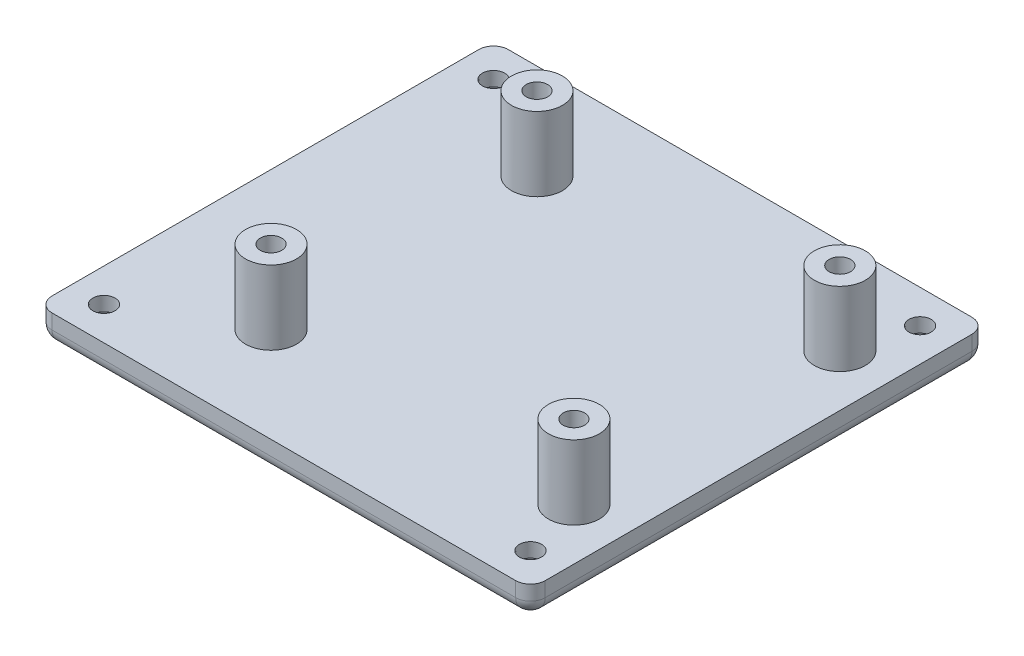
SolidWorks part; units mm, degrees
ref_plane "Front Plane" through (0, 0, 0) normal (0, 0, 1) x (1, 0, 0)
ref_plane "Top Plane" through (0, 0, 0) normal (0, 1, 0) x (1, 0, 0)
ref_plane "Right Plane" through (0, 0, 0) normal (1, 0, 0) x (0, 0, -1)
sketch "Sketch1" plane through (0, 0, 0) normal (0, 1, 0) x (1, 0, 0)
  line L1 (0, 0) -> (66.76, 0)
  line L2 (0, 0) -> (0, 61.76)
  line L3 (0, 61.76) -> (66.76, 61.76)
  line L4 (66.76, 0) -> (66.76, 61.76)
  dimension "D1" = 66.76
  dimension "D2" = 61.76
extrude "Boss-Extrude3" add sketch "Sketch1" against normal blind 4
sketch "Sketch2" plane through (0, 0, 0) normal (0, 1, 0) x (1, 0, 0)
  line L0 (63.76, 8.88) -> (14.76, 8.88) construction
  line L1 (0, 61.76) -> (0, 0) construction
  line L2 (18.76, 12.88) -> (59.76, 12.88) construction
  line L3 (0, 0) -> (66.76, 0) construction
  line L4 (66.76, 0) -> (66.76, 61.76) construction
  line L5 (66.76, 61.76) -> (0, 61.76) construction
  line L6 (63.76, 59.75) -> (63.76, 2.01) construction
  line L7 (2.01, 2.01) -> (64.75, 2.01) construction
  line L8 (2.01, 2.01) -> (2.01, 59.75) construction
  line L9 (2.01, 59.75) -> (64.75, 59.75) construction
  line L10 (64.75, 2.01) -> (64.75, 59.75) construction
  line L11 (18.76, 12.88) -> (18.76, 48.88) construction
  line L12 (18.76, 48.88) -> (59.76, 48.88) construction
  line L13 (59.76, 12.88) -> (59.76, 48.88) construction
  line L14 (14.76, 8.88) -> (14.76, 52.88) construction
  line L15 (14.76, 52.88) -> (63.76, 52.88) construction
  line L16 (0, 30.88) -> (66.76, 30.88) construction
  line L17 (39.26, 12.88) -> (39.26, 48.88) construction
  circle A0 centre (59.76, 12.88) radius 1.45
  circle A4 centre (59.76, 12.88) radius 3.45
  circle A5 centre (18.76, 12.88) radius 3.45
  circle A6 centre (18.76, 12.88) radius 1.45
  circle A7 centre (18.76, 48.88) radius 1.45
  circle A8 centre (59.76, 48.88) radius 1.45
  circle A9 centre (59.76, 48.88) radius 3.45
  circle A10 centre (18.76, 48.88) radius 3.45
  dimension "D13" = 2.9
  dimension "D11" = 6.9
  dimension "D1" = 2.01
  dimension "D2" = 2.01
  dimension "D3" = 0.99
  dimension "D4" = 2.01
  dimension "D5" = 2.01
  dimension "D6" = 49
  dimension "D7" = 44
  dimension "D8" = 22
  dimension "D9" = 4
  dimension "D10" = 4
  dimension "D12" = 4
extrude "Boss-Extrude4" add sketch "Sketch2" along normal blind 10
sketch "Sketch3" plane through (0, 0, 0) normal (0, 1, 0) x (1, 0, 0)
  line L0 (0, 61.76) -> (0, 0) construction
  line L1 (33.38, 59.75) -> (33.38, 2.01) construction
  line L2 (2.01, 30.88) -> (64.75, 30.88) construction
  line L3 (2.01, 59.75) -> (64.75, 59.75) construction
  line L6 (2.01, 59.75) -> (2.01, 2.01) construction
  line L11 (2.01, 2.01) -> (64.75, 2.01) construction
  line L12 (64.75, 59.75) -> (64.75, 2.01) construction
  line L13 (0, 0) -> (66.76, 0) construction
  line L14 (66.76, 61.76) -> (0, 61.76) construction
  line L15 (66.76, 0) -> (66.76, 61.76) construction
  circle A0 centre (4.51, 57.25) radius 1.5
  circle A1 centre (62.25, 57.25) radius 1.5
  circle A2 centre (62.25, 4.51) radius 1.5
  circle A3 centre (4.51, 4.51) radius 1.5
  dimension "D5" = 3
  dimension "D1" = 2.01
  dimension "D2" = 2.01
  dimension "D3" = 2.01
  dimension "D4" = 2.01
  dimension "D6" = 2.5
  dimension "D7" = 2.5
extrude "Cut-Extrude1" cut sketch "Sketch3" against normal blind 3 draft 3 draft outward yes
sketch "Sketch5" plane through (0, -4, 0) normal (0, -1, 0) x (1, 0, 0)
  line L0 (33.38, -4.51) -> (33.38, -57.6662) construction
  line L1 (4.51, -4.51) -> (62.25, -4.51) construction
  line L2 (4.51, -4.51) -> (4.51, -57.25) construction
  line L3 (4.51, -57.25) -> (62.25, -57.25) construction
  line L4 (62.25, -4.51) -> (62.25, -57.25) construction
  line L5 (4.51, -30.88) -> (62.25, -30.88) construction
  circle A0 centre (4.51, -4.51) radius 3
  circle A1 centre (62.25, -4.51) radius 3
  circle A2 centre (62.25, -57.25) radius 3
  circle A3 centre (4.51, -57.25) radius 3
  point P10 (33.38, -30.88)
  dimension "D1" = 6
fillet "Fillet2" radius 2 4 edges at (0, -2, 0) (66.76, -2, 0) (66.76, -2, -61.76) (0, -2, -61.76)
fillet "Fillet1" radius 2 8 edges at (66.76, -4, -30.88) (33.38, -4, -61.76) (0, -4, -30.88) (33.38, -4, 0) (0.5858, -4, -0.5858) (0.5858, -4, -61.1742) (66.1742, -4, -61.1742) (66.1742, -4, -0.5858)
extrude "Cut-Extrude2" cut sketch "Sketch5" against normal blind 2 draft 1
sketch "Sketch6" plane through (0, -4, 0) normal (0, -1, 0) x (1, 0, 0)
  line L0 (33.38, -59.76) -> (33.38, -2) construction
  line L1 (6.1531, -59.76) -> (60.6069, -59.76) construction
  line L2 (60.6069, -2) -> (6.1531, -2) construction
  line L3 (64.76, -54.76) -> (2, -54.76) construction
  line L4 (64.76, -55.6069) -> (64.76, -6.1531) construction
  line L5 (2, -6.1531) -> (2, -55.6069) construction
  line L6 (62.25, -4.51) -> (62.25, -54.76) construction
  line L7 (35.88, -54.76) -> (35.88, -2) construction
  line L8 (30.88, -54.76) -> (30.88, -2) construction
  line L9 (4.51, -4.51) -> (4.51, -54.76) construction
  line L10 (62.25, -50.76) -> (35.88, -50.76) construction
  line L11 (49.065, -50.76) -> (49.065, -2) construction
  line L12 (30.87, -50.76) -> (4.5, -50.76) construction
  line L13 (30.87, -46.76) -> (4.5, -46.76) construction
  line L14 (30.87, -42.76) -> (4.5, -42.76) construction
  line L15 (30.87, -38.76) -> (4.5, -38.76) construction
  line L16 (30.87, -34.76) -> (4.5, -34.76) construction
  line L17 (30.87, -30.76) -> (4.5, -30.76) construction
  line L18 (30.87, -26.76) -> (4.5, -26.76) construction
  line L19 (30.87, -22.76) -> (4.5, -22.76) construction
  line L20 (30.87, -18.76) -> (4.5, -18.76) construction
  line L21 (30.87, -14.76) -> (4.5, -14.76) construction
  line L22 (30.87, -10.76) -> (4.5, -10.76) construction
  line L23 (30.87, -6.76) -> (4.5, -6.76) construction
  line L24 (62.25, -46.76) -> (35.88, -46.76) construction
  line L25 (62.25, -42.76) -> (35.88, -42.76) construction
  line L26 (62.25, -38.76) -> (35.88, -38.76) construction
  line L27 (62.25, -34.76) -> (35.88, -34.76) construction
  line L28 (62.25, -30.76) -> (35.88, -30.76) construction
  line L29 (62.25, -26.76) -> (35.88, -26.76) construction
  line L30 (62.25, -22.76) -> (35.88, -22.76) construction
  line L31 (62.25, -18.76) -> (35.88, -18.76) construction
  line L32 (62.25, -14.76) -> (35.88, -14.76) construction
  line L33 (62.25, -10.76) -> (35.88, -10.76) construction
  line L34 (62.25, -6.76) -> (35.88, -6.76) construction
  line L35 (62.25, -2) -> (35.88, -2) construction
  line L36 (30.88, -2) -> (4.51, -2) construction
  line L37 (62.25, -4.51) -> (62.25, -1.9267) construction
  line L38 (35.88, -2.76) -> (62.25, -2.76) construction
  line L39 (30.88, -2.76) -> (4.51, -2.76) construction
  text T0 "<b>Reference</b>" font "Century Gothic" height 3.5
  text T1 "<b>A . -</b>" font "Century Gothic" height 2.5
  text T2 "<b>B - . . .</b>"
  text T3 "C - . - ."
  text T4 "D - . ."
  text T5 "<b>E .</b>"
  text T6 "<b>F . . - .</b>"
  text T7 "<b>G - - .</b>"
  text T8 "<b>H . . . .</b>"
  text T9 "<b>I . .</b>"
  text T10 "<b>J . - - -</b>"
  text T11 "<b>K - . -</b>"
  text T12 "<b>L . - . .</b>"
  text T13 "<b>M - -</b>"
  text T14 "<b>N - .</b>"
  text T15 "<b>O - - -</b>" font "CMU Serif" height 2.5
  text T16 "<b>P . - - .</b>"
  text T17 "<b>Q - - . -</b>"
  text T18 "<b>R . - .</b>"
  text T19 "<b>S . . .</b>"
  text T20 "<b>T -</b>"
  text T21 "<b>U . . -</b>"
  text T22 "<b>V . . . -</b>"
  text T23 "<b>W . - -</b>"
  text T24 "<b>X - . . -</b>"
  text T25 "<b>Y - . - -</b>"
  text T26 "<b>Z - - . .</b>"
  dimension "D1" = 5
  dimension "D2" = 2.5
  dimension "D3" = 4
  dimension "D4" = 13.185
  dimension "D5" = 2
  dimension "D7" = 0.76
  dimension "D6" = 12
extrude "Cut-Extrude3" cut sketch "Sketch6" against normal blind 1
